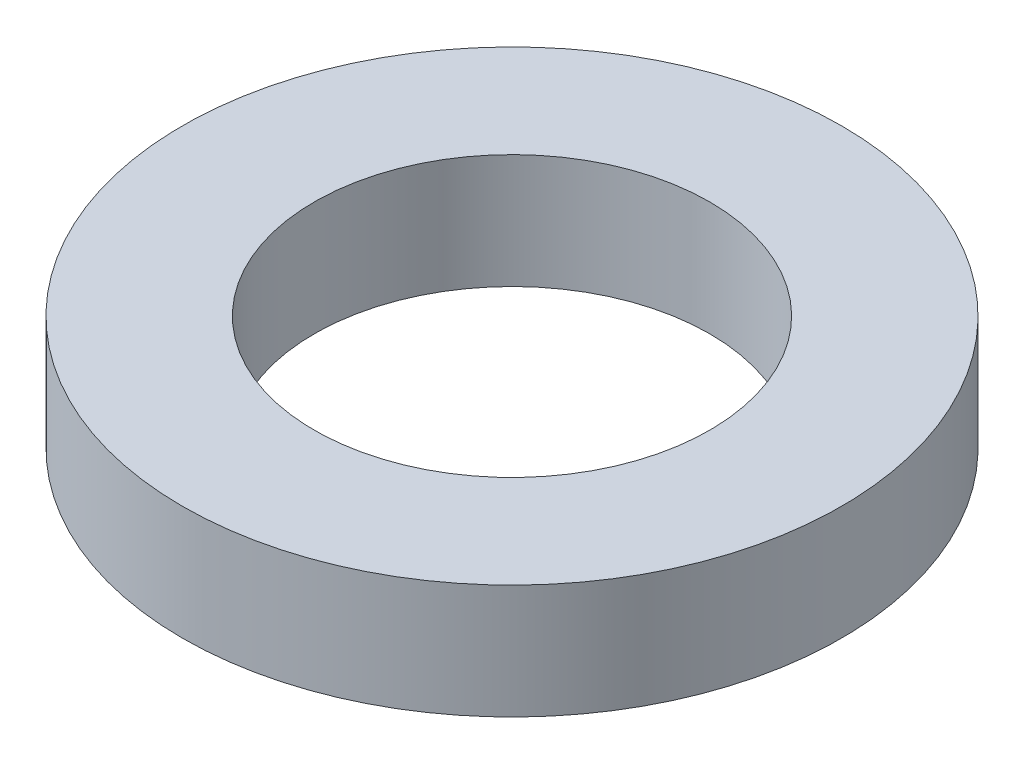
SolidWorks part; units mm, degrees
ref_plane "Front Plane" through (0, 0, 0) normal (0, 0, 1) x (1, 0, 0)
ref_plane "Top Plane" through (0, 0, 0) normal (0, 1, 0) x (1, 0, 0)
ref_plane "Right Plane" through (0, 0, 0) normal (1, 0, 0) x (0, 0, -1)
sketch "Sketch1" plane through (0, 0, 0) normal (0, 1, 0) x (1, 0, 0)
  circle A0 centre (0, 0) radius 75
  dimension "FLANGE_OD" = 150
extrude "Boss-Extrude1" add sketch "Sketch1" along normal blind 26
sketch "Sketch2" plane through (0, 0, 0) normal (0, 1, 0) x (1, 0, 0)
  circle A0 centre (0, 0) radius 45
  dimension "BORE_D" = 90
extrude "Cut-Extrude1" cut sketch "Sketch2" along normal through all
sketch "Sketch3" plane through (0, 26, 0) normal (0, 1, 0) x (1, 0, 0)
  circle A0 centre (0, 0) radius 34.9359 construction
  circle A1 centre (-34.9359, 0) radius 3.1998
  dimension "BOLT_D" = 6.3996
  dimension "BOLT_PCD" = 69.8717
extrude "Cut-Extrude2" cut sketch "Sketch3" against normal blind 20.9403 rebuild error yes
pattern_circular "CirPattern1" count 5 over 360 rebuild error yes
